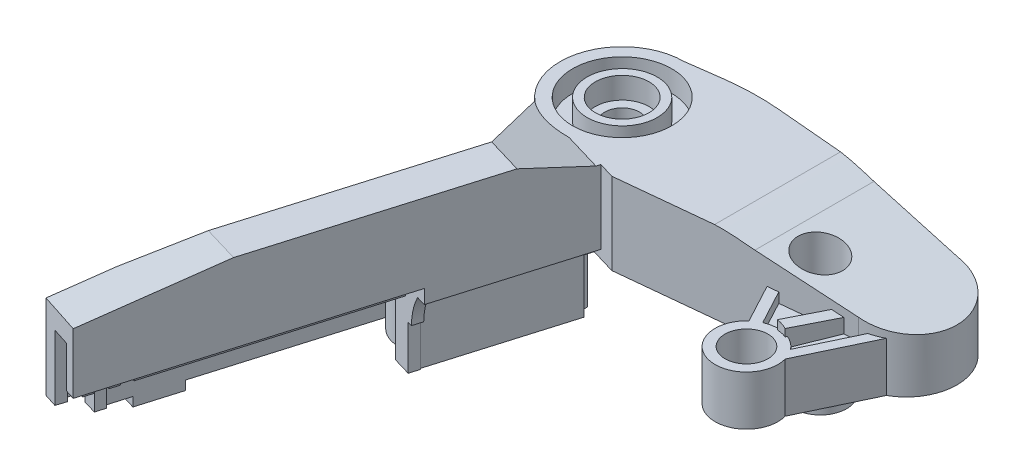
SolidWorks part; units mm, degrees
material "ABS"
ref_plane "Front Plane" through (0, 0, 0) normal (0, 0, 1) x (1, 0, 0)
ref_plane "Top Plane" through (0, 0, 0) normal (0, 1, 0) x (1, 0, 0)
ref_plane "Right Plane" through (0, 0, 0) normal (1, 0, 0) x (0, 0, -1)
sketch "Sketch1" plane through (0, 0, 0) normal (0, 1, 0) x (1, 0, 0)
  line L0 (0, 7.5) -> (4.1394, 8.0569)
  line L1 (10.7438, 8.2115) -> (34.4, 6.15)
  line L2 (2, -7.2284) -> (7.6561, -8.9073)
  line L3 (7.6561, -8.9073) -> (34.7881, -6.1377)
  arc A0 (0, 7.5) -> (2, -7.2284) centre (0, 0) ccw
  arc A1 (34.7881, -6.1377) -> (34.4, 6.15) centre (34.4, 0) ccw
  arc A2 (4.1394, 8.0569) -> (10.7438, 8.2115) centre (8.1394, -21.6752) cw
  point P12 (7.433, 8.5)
  dimension "D1" = 15
  dimension "D3" = 12.3
  dimension "D8" = 30
  dimension "D2" = 34.4
  dimension "D4" = 7.5
  dimension "D5" = 1
  dimension "D6" = 5.9
  dimension "D7" = 2
extrude "Boss-Extrude1" add sketch "Sketch1" along normal blind 9.9
ref_plane "Plane1" through (0, 0, 10) normal (0, 0, 1) x (1, 0, 0)
sketch "Sketch2" plane through (0, 0, 10) normal (0, 0, 1) x (1, 0, 0)
  line L0 (7.6561, 9.9) -> (34.7881, 9.9) construction
  line L1 (23.3819, 9.2098) -> (40.55, 6.3)
  line L2 (40.55, 0) -> (40.55, 9.9) construction
  line L3 (34.4, 0) -> (40.55, 0) construction
  line L4 (40.55, 6.3) -> (40.55, 9.9)
  line L5 (40.55, 9.9) -> (18.9463, 9.9)
  spline S0 degree 3 poles (18.9463, 9.9) (20.4431, 9.8135) (21.9158, 9.5021) (23.3819, 9.2098) knots 0 0 0 0 1 1 1 1
  dimension "D1" = 0
  dimension "D2" = 6.3
extrude "Cut-Extrude1" cut sketch "Sketch2" against normal through all
ref_plane "Plane2" through (0, 0, 0) normal (0, -1, 0) x (-1, 0, 0)
sketch "Sketch3" plane through (0, 0, 0) normal (0, -1, 0) x (-1, 0, 0)
  line L0 (-37.3784, -5.3807) -> (-33.4231, -13.6871)
  line L1 (-27.2334, -11.8704) -> (-24.7109, -7.1664)
  line L2 (-7.6561, -8.9073) -> (-34.7881, -6.1377) construction
  line L3 (-34.7881, -6.1377) -> (-24.7109, -7.1664)
  arc A0 (-34.4, 6.15) -> (-34.7881, -6.1377) centre (-34.4, 0) ccw construction
  arc A1 (-33.4231, -13.6871) -> (-27.2334, -11.8704) centre (-29.7624, -14.7067) ccw
  arc A2 (-37.3784, -5.3807) -> (-34.7881, -6.1377) centre (-34.4, 0) ccw
  dimension "D2" = 7.6
extrude "Boss-Extrude2" add sketch "Sketch3" against normal blind 6
sketch "Sketch4" plane through (0, 6, 0) normal (0, 1, 0) x (1, 0, 0)
  line L1 (26.0019, -7.0346) -> (28.2473, -11.2218)
  line L2 (35.7549, -5.9989) -> (32.7354, -12.34)
  line L4 (27.2334, -11.8704) -> (24.7109, -7.1664) construction
  line L5 (24.7109, -7.1664) -> (34.7881, -6.1377) construction
  line L6 (37.3784, -5.3807) -> (33.4231, -13.6871) construction
  line L7 (26.0019, -7.0346) -> (34.7126, -6.1454)
  arc A2 (32.7354, -12.34) -> (28.2473, -11.2218) centre (29.7624, -14.7067) ccw
  arc A3 (34.7881, -6.1377) -> (37.3784, -5.3807) centre (34.4, 0) ccw construction
  arc A4 (35.7549, -5.9989) -> (34.7881, -6.1377) centre (34.4, 0) cw
  arc M6 (37.3784, -5.3807) -> (34.7881, -6.1377) centre (34.4, 0) cw
  line M7 (34.7881, -6.1377) -> (24.7109, -7.1664)
  dimension "D2" = 1.2
  dimension "D4" = 1.2
extrude "Cut-Extrude3" cut sketch "Sketch4" against normal blind 1.2 and the other way through all contours A2 L2 L1 M6 M7 region at (30.9738, 6, 8.6618)
sketch "Sketch5" plane through (0, 6, 0) normal (0, 1, 0) x (1, 0, 0)
  circle A0 centre (29.7624, -14.7067) radius 2.6
  arc A1 (27.2334, -11.8704) -> (33.4231, -13.6871) centre (29.7624, -14.7067) ccw construction
  dimension "D1" = 1.2
extrude "Cut-Extrude4" cut sketch "Sketch5" against normal through all
sketch "Sketch6" plane through (2.1702, 12.8048, 0) normal (0.1671, 0.9859, 0) x (0.9859, -0.1671, 0)
  line L0 (33.4969, -6.1377) -> (24.8342, -7.0346) construction
  line L1 (24.6337, -7.0346) -> (26.8475, -11.2218) construction
  circle A0 centre (25.2526, -3.0704) radius 2.7
  dimension "D1" = 5.4
  dimension "D2" = 3.9
  dimension "D3" = 2.4
ref_plane "Plane3" through (0, 9.9, 0) normal (0, 1, 0) x (1, 0, 0)
sketch "Sketch7" plane through (0, 9.9, 0) normal (0, 1, 0) x (1, 0, 0)
  circle A0 centre (27.0678, -3.0704) radius 2.7
extrude "Cut-Extrude6" cut sketch "Sketch7" against normal through all
sketch "Sketch8" plane through (0, 9.9, 0) normal (0, 1, 0) x (1, 0, 0)
  circle A0 centre (0, 0) radius 6
  arc A1 (0, 7.5) -> (2, -7.2284) centre (0, 0) ccw construction
  dimension "D1" = 1.5
extrude "Cut-Extrude7" cut sketch "Sketch8" against normal blind 2.6
sketch "Sketch9" plane through (0, 7.3, 0) normal (0, 1, 0) x (1, 0, 0)
  circle A0 centre (0, 0) radius 2.1
  dimension "D1" = 4.2
extrude "Cut-Extrude8" cut sketch "Sketch9" against normal through all
shell "Shell7" thickness 1 removed face at (0, 0, 2.1)
sketch "Sketch10" plane through (0, 7.3, 0) normal (0, 1, 0) x (1, 0, 0)
  circle A0 centre (0, 0) radius 4.25
  circle A1 centre (0, 0) radius 3.25
  dimension "D1" = 8.5
  dimension "D2" = 1
extrude "Boss-Extrude3" add sketch "Sketch10" along normal up to surface (2.6 mm away) up to face at (0, 9.9, 6)
sketch "Sketch11" plane through (0, 0, 0) normal (0, -1, 0) x (1, 0, 0)
  circle A0 centre (27.0678, 3.0704) radius 3.7
extrude "Boss-Extrude4" add sketch "Sketch11" along normal blind 6.1
sketch "Sketch12" plane through (0, -6.1, 0) normal (0, -1, 0) x (1, 0, 0)
  circle A0 centre (27.0678, 3.0704) radius 3.2
  circle A1 centre (27.0678, 3.0704) radius 3.7 construction
  circle A2 centre (27.0678, 3.0704) radius 1.9
  circle A3 centre (27.0678, 3.0704) radius 3.7
  circle M1 centre (27.0678, 3.0704) radius 3.7
  dimension "D1" = 0.5
  dimension "D2" = 1.3
extrude "Cut-Extrude10" cut sketch "Sketch12" against normal blind 1.9 contours A0 M1 | A2 region at (27.0678, -6.1, 3.0704) region at (23.4725, -6.1, 3.0704)
sketch "Sketch13" plane through (0, -4.2, 0) normal (0, -1, 0) x (1, 0, 0)
  circle A0 centre (27.0678, 3.0704) radius 1.15
  dimension "D1" = 2.3
extrude "Cut-Extrude11" cut sketch "Sketch13" against normal through all
sketch "Sketch14" plane through (0, 9.9, 0) normal (0, 1, 0) x (1, 0, 0)
  line L0 (5.7636, -8.3456) -> (-8.8626, -57.6206)
  line L1 (2, -7.2284) -> (7.6561, -8.9073) construction
  line L2 (-5.9463, -4.5707) -> (-20.5726, -53.8458)
  line L3 (-20.5726, -53.8458) -> (-8.8626, -57.6206)
  line L4 (2, -7.2284) -> (5.7636, -8.3456)
  arc A0 (0, 7.5) -> (2, -7.2284) centre (0, 0) ccw construction
  arc A1 (-5.9463, -4.5707) -> (2, -7.2284) centre (0, 0) ccw
  dimension "D1" = 51.4
  dimension "D2" = 12.3
extrude "Boss-Extrude5" add sketch "Sketch14" against normal blind 17.9 and the other way blind 2.3
sketch "Sketch15" plane through (-17.6606, 0, 54.7845) normal (-0.3068, 0, 0.9518) x (0.9518, 0, 0.3068)
  line L3 (-3.0595, -8) -> (-3.0595, 12.2) construction
  line L4 (-3.0595, -1.6) -> (-0.9867, -0.2073)
  line L5 (-0.9867, -0.2073) -> (3.6438, 9.9)
  line L8 (3.6438, 9.9) -> (-3.0595, 9.9)
  line L9 (-3.0595, 9.9) -> (-3.0595, -1.6)
  point P0 (0, 0)
sketch "Sketch18" plane through (-17.6606, 0, 54.7845) normal (-0.3068, 0, 0.9518) x (0.9518, 0, 0.3068)
  line L0 (3.6438, 9.9) -> (4.6975, 12.2)
  line L1 (-3.0595, 12.2) -> (9.2438, 12.2) construction
  line L2 (4.6975, 12.2) -> (-3.0595, 12.2)
  line L3 (-3.0595, 12.2) -> (-3.0595, -1.6)
  line L4 (-3.0595, -1.6) -> (-0.9867, -0.2073)
  line L5 (-0.9867, -0.2073) -> (3.6438, 9.9)
extrude "Cut-Extrude15" cut sketch "Sketch18" along direction (0.2846, 0, -0.9587) on the side against the normal up to surface (51.4 mm away) up to face at (-4.8505, 4.95, -2.3895)
sketch "Sketch19" plane through (0, 12.2, 0) normal (0, 1, 0) x (1, 0, 0)
  line L0 (-0.9173, -14.8809) -> (-4.8967, -5.6809)
  line L1 (1.3076, -7.3851) -> (-13.1897, -56.2258) construction
  line L2 (1.3076, -7.3851) -> (-0.9173, -14.8809)
  arc A0 (0, 7.5) -> (0.1753, -7.498) centre (0, 0) ccw construction
  arc A1 (-4.8967, -5.6809) -> (1.3076, -7.3851) centre (0, 0) ccw
  dimension "D1" = 9.2
extrude "Boss-Extrude6" add sketch "Sketch19" against normal up to next
ref_plane "Plane4" through (-4.218, 0, -1.252) normal (-0.9587, 0, -0.2846) x (-0.2846, 0, 0.9587)
sketch "Sketch20" plane through (-4.218, 0, -1.252) normal (-0.9587, 0, -0.2846) x (-0.2846, 0, 0.9587)
  line L0 (6.8394, 9.9) -> (14.5267, 12.2)
  line L1 (58.6524, 9.8764) -> (42.1362, 12.2)
  line L3 (14.5267, 12.2) -> (57.6545, 12.2) construction
  line L4 (6.8394, 0) -> (6.8394, 9.9) construction
  line L7 (58.6524, 9.8764) -> (58.6524, 14.2029)
  line L8 (58.6524, 14.2029) -> (42.1362, 14.2029)
  line L10 (42.1362, 14.2029) -> (42.1362, 12.2)
  line L11 (6.8394, 9.9) -> (6.8394, 14.378)
  line L12 (6.8394, 14.378) -> (14.5267, 14.378)
  line L13 (14.5267, 14.378) -> (14.5267, 12.2)
extrude "Cut-Extrude17" cut sketch "Sketch20" against normal through all
sketch "Sketch22" plane through (-1.9462, 0, 6.5567) normal (-0.2846, 0, 0.9587) x (0.9587, 0, 0.2846)
  line L0 (3.0777, 12.2) -> (3.0777, 9.9)
  line L1 (3.0777, 9.9) -> (7.9001, 9.9)
  line L2 (7.9001, 9.9) -> (7.9001, 12.2)
  line L3 (7.9001, 12.2) -> (3.0777, 12.2)
extrude "Cut-Extrude19" cut sketch "Sketch22" against normal through all
sketch "Sketch23" plane through (-4.218, 0, -1.252) normal (-0.9587, 0, -0.2846) x (-0.2846, 0, 0.9587)
  line L0 (57.5221, -0.2073) -> (49.9221, -0.2073)
  line L1 (7.7359, -0.2073) -> (57.5221, -0.2073) construction
  line L2 (49.9221, -0.2073) -> (49.9221, -8)
  line L3 (6.0738, -8) -> (57.4738, -8) construction
  line L4 (49.9221, -8) -> (58.9262, -8)
  line L5 (58.9262, -8) -> (58.9262, -0.2073)
  line L6 (58.9262, -0.2073) -> (57.5221, -0.2073)
  dimension "D1" = 7.6
extrude "Cut-Extrude20" cut sketch "Sketch23" against normal through all
sketch "Sketch25" plane through (-4.218, 0, -1.252) normal (-0.9587, 0, -0.2846) x (-0.2846, 0, 0.9587)
  line L0 (49.9221, -0.2073) -> (57.5221, -0.2073) construction
  line L1 (57.366, -0.2073) -> (49.9221, -0.2073)
  line L2 (49.9221, -0.2073) -> (49.9221, 11.1046)
  line L3 (49.9221, 11.1046) -> (57.6157, 10.0223)
  line L4 (57.6157, 10.0223) -> (57.9672, -0.2073)
  line L5 (57.9672, -0.2073) -> (57.366, -0.2073)
  line L6 (57.6313, 10.0201) -> (42.1362, 12.2) construction
  point P9 (0, 0)
extrude "Cut-Extrude21" cut sketch "Sketch25" against normal blind 7.2
sketch "Sketch26" plane through (-17.6606, 0, 54.7845) normal (-0.3068, 0, 0.9518) x (0.9518, 0, 0.3068)
  line L8 (9.2438, 10.0019) -> (3.6988, 10.0201) construction
  line L9 (3.6988, 10.0201) -> (3.5414, 9.6764)
  line L10 (3.5414, 9.6764) -> (4.1424, 9.2688)
  line L11 (4.1424, 9.2688) -> (4.1399, 10.0187)
  line L12 (3.6988, 10.0201) -> (3.6988, 10.1539)
  line L13 (3.6988, 10.1539) -> (4.1399, 10.1539)
  line L14 (4.1399, 10.1539) -> (4.1399, 10.0187)
extrude "Cut-Extrude26" cut sketch "Sketch26" along direction (0.2846, 0, -0.9587) on the side against the normal blind 7.2
ref_plane "Plane5" through (0, -8, 0) normal (0, -1, 0) x (-1, 0, 0)
sketch "Sketch28" plane through (0, -8, 0) normal (0, -1, 0) x (-1, 0, 0)
  line L0 (7.8851, -11.1024) -> (7.1693, -2.2024)
  line L2 (5.9463, -4.5707) -> (18.4237, -46.6063) construction
  line L3 (7.8851, -11.1024) -> (5.9463, -4.5707)
  arc A1 (4.8967, -5.6809) -> (0, 7.5) centre (0, 0) ccw construction
  arc A2 (7.1693, -2.2024) -> (5.9463, -4.5707) centre (0, 0) cw
  dimension "D1" = 8.9
extrude "Boss-Extrude9" add sketch "Sketch28" against normal blind 6.4
sketch "Sketch29" plane through (0, -8, 0) normal (0, -1, 0) x (-1, 0, 0)
  line L0 (7.8851, -11.1024) -> (7.1693, -2.2024) construction
  line L1 (-2, -7.2284) -> (-1.999, -6.185)
  line L2 (7.1693, -2.2024) -> (6.1155, -2.2024)
  arc A0 (-2, -7.2284) -> (7.1693, -2.2024) centre (0, 0) ccw
  arc A1 (4.8967, -5.6809) -> (0, 7.5) centre (0, 0) ccw construction
  arc A2 (-1.999, -6.185) -> (6.1155, -2.2024) centre (0, 0) ccw
  arc A3 (-1.999, -6.185) -> (-0.0646, 6.4997) centre (0, 0) ccw construction
extrude "Boss-Extrude10" add sketch "Sketch29" against normal up to surface (8 mm away) up to face at (29.7624, 0, 17.3067)
sketch "Sketch30" plane through (0, -8, 0) normal (0, -1, 0) x (1, 0, 0)
  line L0 (-11.2829, 47.4741) -> (-4.123, 23.3527)
  line L1 (-6.6322, 50.1063) -> (-18.4237, 46.6063) construction
  line L2 (-4.123, 23.3527) -> (-9.7719, 21.6759)
  line L3 (-9.7719, 21.6759) -> (-16.9318, 45.7973)
  line L4 (-16.9318, 45.7973) -> (-11.2829, 47.4741)
  line L5 (-7.8851, 11.1024) -> (-18.4237, 46.6063) construction
  line L6 (5.7636, 8.3456) -> (2, 7.2284) construction
  dimension "D1" = 1.2
  dimension "D2" = 1.2
  dimension "D3" = 17.2
extrude "Cut-Extrude27" cut sketch "Sketch30" against normal offset from surface (15.8719 mm away) 1.2 up to face at (-8.9731, 7.6603, 34.7137)
sketch "Sketch31" plane through (0, -8, 0) normal (0, -1, 0) x (1, 0, 0)
  line L0 (-10.1325, 47.8156) -> (-2.9726, 23.6941)
  line L1 (-2.9726, 23.6941) -> (-0.2812, 24.493)
  line L2 (-0.2812, 24.493) -> (-7.4411, 48.6144)
  line L3 (-7.4411, 48.6144) -> (-10.1325, 47.8156)
  line L4 (-4.123, 23.3527) -> (-11.2829, 47.4741) construction
  line L5 (-6.6322, 50.1063) -> (5.7636, 8.3456) construction
  line L6 (-6.6322, 50.1063) -> (-18.4237, 46.6063) construction
  line L7 (-9.7719, 21.6759) -> (-4.123, 23.3527) construction
  dimension "D1" = 1.2
  dimension "D2" = 1.2
  dimension "D3" = 1.2
extrude "Cut-Extrude29" cut sketch "Sketch31" against normal blind 18
sketch "Sketch32" plane through (0, -8, 0) normal (0, -1, 0) x (1, 0, 0)
  line L2 (-11.6244, 48.6245) -> (-10.474, 48.966)
  line L3 (-6.6322, 50.1063) -> (-11.5213, 48.6551) construction
  line L4 (-10.474, 48.966) -> (-2.9726, 23.6941)
  line L5 (-2.9726, 23.6941) -> (-4.123, 23.3527)
  line L12 (-4.123, 23.3527) -> (-11.6244, 48.6245)
  line L13 (-10.1325, 47.8156) -> (-2.9726, 23.6941) construction
extrude "Cut-Extrude39" cut sketch "Sketch32" against normal up to surface (7.7927 mm away) up to face at (-10.1835, -0.2073, 53.1094)
sketch "Sketch33" plane through (0, -8, 0) normal (0, -1, 0) x (1, 0, 0)
  line L0 (-11.6244, 48.6245) -> (-11.2829, 47.4741)
  line L1 (-11.6244, 48.6245) -> (-11.2829, 47.4741) construction
  line L2 (-11.2829, 47.4741) -> (-16.5027, 45.9247)
  line L3 (-11.2829, 47.4741) -> (-16.9318, 45.7973) construction
  line L4 (-16.5027, 45.9247) -> (-16.8442, 47.0751)
  line L5 (-11.6244, 48.6245) -> (-18.4237, 46.6063) construction
  line L6 (-16.8442, 47.0751) -> (-11.6244, 48.6245)
  line L7 (-11.5213, 48.6551) -> (-11.6244, 48.6245) construction
extrude "Cut-Extrude41" cut sketch "Sketch33" against normal up to vertex up to point (-18.4237, -1.6, 46.6063)
sketch "Sketch34" plane through (-13.8642, 0, 46.7079) normal (-0.2846, 0, 0.9587) x (0.9587, 0, 0.2846)
  line L0 (-2.7523, -1.6) -> (-1.6455, -1.6)
  line L1 (-1.6455, -1.6) -> (-2.7523, -4.0164)
  line L2 (-2.7523, -4.0164) -> (-2.7523, -1.6)
extrude "Cut-Extrude42" cut sketch "Sketch34" against normal up to surface (25.1616 mm away) up to face at (-4.2872, 0.8079, 23.3039)
sketch "Sketch35" plane through (-14.2057, 0, 47.8583) normal (-0.2846, 0, 0.9587) x (0.9587, 0, 0.2846)
  line L0 (2.6927, -0.2073) -> (-0.68, -0.2073)
  line L1 (-0.68, -0.2073) -> (-2.7523, -1.6)
  line L2 (-4.3999, -1.6) -> (-2.3276, -0.2073) construction
  line L3 (-2.7523, -1.6) -> (2.6927, -1.6)
  line L4 (2.6927, -1.6) -> (2.6927, -0.2073)
extrude "Cut-Extrude43" cut sketch "Sketch35" against normal up to surface (26.3616 mm away) up to face at (-5.5695, -0.0684, 22.9233)
sketch "Sketch36" plane through (0, -8, 0) normal (0, -1, 0) x (1, 0, 0)
  line L0 (-10.1325, 47.8156) -> (-10.474, 48.966)
  line L1 (-10.474, 48.966) -> (-6.6322, 50.1063)
  line L2 (-10.1325, 47.8156) -> (-7.4411, 48.6144)
  line L3 (-7.4411, 48.6144) -> (-0.2812, 24.493)
  line L4 (-0.2812, 24.493) -> (0.8692, 24.8345)
  line L5 (-6.6322, 50.1063) -> (5.7636, 8.3456) construction
  line L6 (0.8692, 24.8345) -> (-6.6322, 50.1063)
extrude "Cut-Extrude44" cut sketch "Sketch36" against normal up to surface (7.7927 mm away) up to face at (-9.9175, -0.2073, 45.2654)
sketch "Sketch37" plane through (0, -0.2073, 0) normal (0, -1, 0) x (1, 0, 0)
  line L0 (-10.1325, 47.8156) -> (-12.3363, 55.24)
  line L1 (-12.3363, 55.24) -> (-9.6635, 56.1017)
  line L2 (-9.6635, 56.1017) -> (-7.4411, 48.6144)
  line L3 (-11.5213, 48.6551) -> (-13.718, 56.0554) construction
  line L4 (-8.8626, 57.6206) -> (0.8692, 24.8345) construction
  line L10 (-13.718, 56.0554) -> (-8.8626, 57.6206) construction
  line L11 (-10.1325, 47.8156) -> (-7.4411, 48.6144)
  dimension "D1" = 1.2
extrude "Cut-Extrude45" cut sketch "Sketch37" against normal up to surface (10.2073 mm away) up to face at (-5.2068, 10, 36.1543)
sketch "Sketch38" plane through (0, -0.2073, 0) normal (0, -1, 0) x (1, 0, 0)
  line L0 (-12.3363, 55.24) -> (-12.7045, 56.3822)
  line L1 (-13.718, 56.0554) -> (-8.8626, 57.6206) construction
  line L2 (-12.7045, 56.3822) -> (-8.8626, 57.6206)
  line L3 (-8.8626, 57.6206) -> (0.8692, 24.8345)
  line L4 (0.8692, 24.8345) -> (-0.2812, 24.493)
  line L5 (-0.2812, 24.493) -> (-9.6635, 56.1017)
  line L6 (-9.6635, 56.1017) -> (-12.3363, 55.24)
extrude "Cut-Extrude46" cut sketch "Sketch38" against normal blind 2.9
sketch "Sketch39" plane through (0, 2.6927, 0) normal (0, -1, 0) x (1, 0, 0)
  line L0 (-9.6635, 56.1017) -> (-10.0317, 57.2438)
  line L1 (-8.8626, 57.6206) -> (-12.7045, 56.3822) construction
  line L2 (-10.0317, 57.2438) -> (-12.7045, 56.3822)
  line L3 (-12.7045, 56.3822) -> (-12.3363, 55.24)
  line L4 (-12.3363, 55.24) -> (-9.6635, 56.1017)
extrude "Cut-Extrude47" cut sketch "Sketch39" against normal blind 5
sketch "Sketch40" plane through (0, -8, 0) normal (0, -1, 0) x (1, 0, 0)
  line L0 (-6.2067, 4.2104) -> (-7.066, 14.8953)
  line L1 (-7.8851, 11.1024) -> (-7.1693, 2.2024) construction
  line L3 (-1.862, 19.1612) -> (1.6543, 7.3153)
  line L4 (0.8692, 24.8345) -> (5.7636, 8.3456) construction
  arc A0 (1.6543, 7.3153) -> (-6.2067, 4.2104) centre (0, 0) ccw
  arc A1 (-7.066, 14.8953) -> (-1.862, 19.1612) centre (-5.3611, 18.1226) ccw
  circle A3 centre (-5.3611, 18.1226) radius 2.45
  dimension "D1" = 7.3
  dimension "D3" = 1.2
extrude "Cut-Extrude48" cut sketch "Sketch40" against normal blind 6
sketch "Sketch41" plane through (0, -8, 0) normal (0, -1, 0) x (1, 0, 0)
  line L0 (-9.7719, 21.6759) -> (-8.9325, 18.8479)
  line L3 (-7.8851, 11.1024) -> (-18.4237, 46.6063) construction
  line L4 (-4.123, 23.3527) -> (-3.5007, 21.2563)
  line L5 (-9.7719, 21.6759) -> (-4.123, 23.3527)
  arc A0 (-3.5007, 21.2563) -> (-8.9325, 18.8479) centre (-5.3611, 18.1226) ccw
extrude "Cut-Extrude49" cut sketch "Sketch41" against normal up to surface (3.0063 mm away) up to face at (-9.5465, 3.6732, 34.8662)
sketch "Sketch42" plane through (0, -8, 0) normal (0, -1, 0) x (1, 0, 0)
  line L0 (2.6053, 8.3283) -> (-1.6966, 22.8211)
  line L1 (-1.6966, 22.8211) -> (0.0603, 23.3426)
  line L2 (0.0603, 23.3426) -> (4.3622, 8.8498)
  line L3 (4.3622, 8.8498) -> (2.6053, 8.3283)
  line L4 (1.6543, 7.3153) -> (-1.862, 19.1612) construction
  line L5 (0.8692, 24.8345) -> (5.7636, 8.3456) construction
  line L6 (-2.9726, 23.6941) -> (-0.2812, 24.493) construction
  dimension "D1" = 1.2
  dimension "D2" = 1.2
  dimension "D3" = 1.2
extrude "Cut-Extrude51" cut sketch "Sketch42" against normal blind 17
sketch "Sketch43" plane through (0, -8, 0) normal (0, -1, 0) x (1, 0, 0)
  line L0 (-0.2812, 24.493) -> (4.6132, 8.0041)
  line L1 (2, 7.2284) -> (5.7636, 8.3456) construction
  line L2 (4.6132, 8.0041) -> (5.7636, 8.3456)
  line L3 (5.7636, 8.3456) -> (0.8692, 24.8345)
  line L4 (0.8692, 24.8345) -> (-0.2812, 24.493)
extrude "Cut-Extrude52" cut sketch "Sketch43" against normal blind 9
sketch "Sketch45" plane through (-6.7043, 0, 22.5865) normal (-0.2846, 0, 0.9587) x (0.9587, 0, 0.2846)
  line L0 (2.6927, -8) -> (6.7001, -8) construction
  line L1 (5.0051, -8) -> (5.0051, -2.6431)
  line L2 (5.0051, -2.6431) -> (5.5843, -2.6431)
  line L3 (6.7001, 1) -> (6.7001, -8)
  line L4 (6.7001, -8) -> (5.0051, -8)
  arc A0 (5.5843, -2.6431) -> (6.7001, 1) centre (13.0545, -2.9387) cw
extrude "Cut-Extrude53" cut sketch "Sketch45" against normal blind 9
sketch "Sketch46" plane through (0, -8, 0) normal (0, -1, 0) x (1, 0, 0)
  line L1 (2.6053, 8.3283) -> (2.8563, 7.4826)
  line L2 (4.6132, 8.0041) -> (2, 7.2284) construction
  line L3 (2.8563, 7.4826) -> (4.6132, 8.0041)
  line L4 (4.6132, 8.0041) -> (4.3622, 8.8498)
  line L5 (4.3622, 8.8498) -> (2.6053, 8.3283)
extrude "Cut-Extrude54" cut sketch "Sketch46" against normal up to surface (8 mm away) up to face at (29.7624, 0, 17.3067)
sketch "Sketch47" plane through (0, -8, 0) normal (0, -1, 0) x (1, 0, 0)
  line L0 (-17.2855, 42.7716) -> (-16.1351, 43.1131)
  line L3 (-16.1351, 43.1131) -> (-14.6838, 38.2239)
  line L5 (-14.6838, 38.2239) -> (-15.8342, 37.8825)
  line L6 (-15.8342, 37.8825) -> (-17.2855, 42.7716)
  line L7 (-16.8442, 47.0751) -> (-18.4237, 46.6063) construction
  point P2 (0, 0)
  point P3 (0, 0)
  point P6 (0, 0)
  point P11 (0, 0)
  dimension "D1" = 4
  dimension "D2" = 5.1
extrude "Boss-Extrude12" add sketch "Sketch47" along normal blind 1.1
sketch "Sketch48" plane through (-4.218, 0, -1.252) normal (-0.9587, 0, -0.2846) x (-0.2846, 0, 0.9587)
  line L0 (40.8221, -9.1) -> (40.8221, -8)
  line L1 (40.8221, -8) -> (45.9221, -8)
  line L2 (45.9221, -8) -> (45.9221, -9.1)
  line L3 (45.9221, -9.1) -> (40.8221, -9.1)
extrude "Boss-Extrude13" add sketch "Sketch48" along normal blind 0.6
ref_plane "Plane6" through (0, -0.2073, 0) normal (0, -1, 0) x (-1, 0, 0)
sketch "Sketch49" plane through (0, -0.2073, 0) normal (0, -1, 0) x (-1, 0, 0)
  line L0 (12.3363, -55.24) -> (11.7652, -55.4241)
  line L1 (11.7652, -55.4241) -> (12.1334, -56.5663)
  line L2 (12.1334, -56.5663) -> (12.7045, -56.3822)
  line L3 (12.7045, -56.3822) -> (12.3363, -55.24) construction
  line L4 (12.3363, -55.24) -> (12.7045, -56.3822)
  line L5 (12.3363, -55.24) -> (9.6635, -56.1017) construction
  line L6 (10.0317, -57.2438) -> (12.7045, -56.3822) construction
  line L7 (12.3363, -55.24) -> (9.6635, -56.1017) construction
  line L8 (10.8723, -50.3081) -> (11.1858, -51.3642)
  line L9 (2.9726, -23.6941) -> (12.3363, -55.24) construction
  line L10 (11.1858, -51.3642) -> (10.6107, -51.535)
  line L11 (10.6107, -51.535) -> (10.2972, -50.4788)
  line L12 (10.2972, -50.4788) -> (10.8723, -50.3081)
  line L13 (11.5213, -48.6551) -> (14.8575, -47.6648) construction
  line L14 (11.6041, -52.7735) -> (11.029, -52.9442)
  line L15 (11.029, -52.9442) -> (11.342, -53.9987)
  line L16 (11.342, -53.9987) -> (11.9172, -53.828)
  line L17 (11.9172, -53.828) -> (11.6041, -52.7735)
  line L18 (9.9105, -49.1763) -> (2.3936, -23.852)
  line L19 (2.3936, -23.852) -> (2.9726, -23.6941)
  line L20 (2.9726, -23.6941) -> (10.4857, -49.0055)
  line L21 (10.4857, -49.0055) -> (9.9105, -49.1763)
  dimension "D1" = 1.1017
  dimension "D2" = 0.6
  dimension "D3" = 0.6
  dimension "D4" = 1.4
  dimension "D5" = 1.1
  dimension "D6" = 1.47
  dimension "D7" = 0.6
  dimension "D8" = 0.6
extrude "Boss-Extrude14" add sketch "Sketch49" against normal up to surface (10.2073 mm away) up to face at (-6.3134, 10, 39.8822)
sketch "Sketch51" plane through (0, 0, 0) normal (0, -1, 0) x (-1, 0, 0)
  line L0 (-29.9191, -11.1101) -> (-33.016, -3.4314)
  line L1 (-34.2037, -3.6948) -> (-31.109, -11.368)
  line L2 (-31.242, -1.928) -> (-30.6804, -2.2709)
  line L3 (-30.7874, -0.7996) -> (-30.2258, -1.1425)
  line L4 (-36.7781, -2.8345) -> (-37.7101, -3.9453)
  line L5 (-38.5383, -3.0654) -> (-37.5689, -1.91)
  line L6 (-36.824, 2.7954) -> (-37.2906, 4.2623)
  line L7 (-35.766, 3.428) -> (-36.213, 4.8336)
  arc A2 (-29.9191, -11.1101) -> (-31.109, -11.368) centre (-29.7624, -14.7067) ccw
  arc A5 (-30.2258, -1.1425) -> (-30.6804, -2.2709) centre (-27.0678, -3.0704) ccw
  arc A6 (-30.7874, -0.7996) -> (-35.769, 3.4374) centre (-34.4, 0) ccw
  arc A7 (-38.5383, -3.0654) -> (-37.7101, -3.9453) centre (-34.4, 0) ccw
  arc A8 (-36.2093, 4.8217) -> (-37.2906, 4.2623) centre (-34.4, 0) ccw
  arc A10 (-36.824, 2.7954) -> (-37.5689, -1.91) centre (-34.4, 0) ccw
  arc A14 (-33.016, -3.4314) -> (-31.242, -1.928) centre (-34.4, 0) ccw
  circle A15 centre (-34.4, 0) radius 2.5
  arc A16 (-36.7781, -2.8345) -> (-34.2037, -3.6948) centre (-34.4, 0) ccw
  dimension "D2" = 1.2
  dimension "D6" = 1.2
  dimension "D3" = 1.2
  dimension "D4" = 1.2
  dimension "D5" = 1.2
extrude "Boss-Extrude15" add sketch "Sketch51" against normal up to surface (5.6267 mm away) contours L4 A16 L1 A2 L0 A14 L2 A5 L3 A6 L7 A8 L6 A10 L5 A7 A15 region at (30.5638, 0, 11.0091) up to face at (29.0881, 7.2284, 0.8826)
